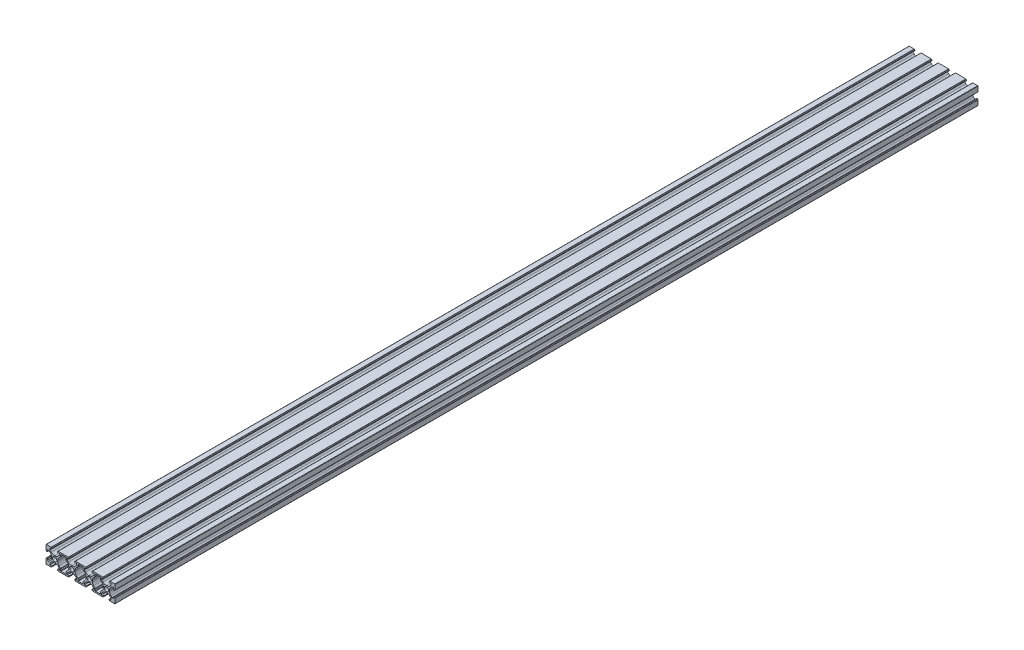
SolidWorks part; units mm, degrees
ref_plane "Plano frontal" through (0, 0, 0) normal (0, 0, 1) x (1, 0, 0)
ref_plane "Plano superior" through (0, 0, 0) normal (0, 1, 0) x (1, 0, 0)
ref_plane "Plano direito" through (0, 0, 0) normal (1, 0, 0) x (0, 0, -1)
sketch "Esboço1" plane through (0, 0, 0) normal (0, 0, 1) x (1, 0, 0)
  line L0 (-9.0343, 3.1) -> (-8.9, 3.1)
  line L3 (-10, 10) -> (-4.0657, 10)
  line L5 (-10, -10) -> (10, 10) construction
  line L6 (-10, 10) -> (10, -10) construction
  line L7 (-8.5, 3.5) -> (-8.5, 5.5)
  line L8 (-10, 0) -> (10, 0) construction
  line L9 (0, 10) -> (0, -10) construction
  line L12 (-8.5, 5.5) -> (-6.5607, 5.5)
  line L15 (-6.5607, 5.5) -> (-5.0645, 4.0038)
  line L16 (-3.6, 0.4683) -> (-3.6, 0)
  line L17 (-0.4683, 3.6) -> (0, 3.6)
  line L18 (-5.5, 6.5607) -> (-4.0038, 5.0645)
  line L21 (-5.5, 8.5) -> (-5.5, 6.5607)
  line L24 (-3.5, 8.5) -> (-5.5, 8.5)
  line L25 (-3.1, 9.0343) -> (-3.1, 8.9)
  line L44 (-10, 4.0657) -> (-10, 10)
  line L45 (-9.8828, 3.7828) -> (-9.3172, 3.2172)
  line L46 (-3.7828, 9.8828) -> (-3.2172, 9.3172)
  line L47 (-3.6, 0) -> (-2.5, 0)
  line L48 (0, 3.6) -> (0, 2.5)
  arc A0 (-3.5, 8.5) -> (-3.1, 8.9) centre (-3.5, 8.9) ccw
  arc A1 (-3.7828, 9.8828) -> (-4.0657, 10) centre (-4.0657, 9.6) ccw
  arc A2 (-10, 4.0657) -> (-9.8828, 3.7828) centre (-9.6, 4.0657) ccw
  arc A3 (-8.5, 3.5) -> (-8.9, 3.1) centre (-8.9, 3.5) cw
  arc A4 (-3.2172, 9.3172) -> (-3.1, 9.0343) centre (-3.5, 9.0343) cw
  arc A5 (-9.3172, 3.2172) -> (-9.0343, 3.1) centre (-9.0343, 3.5) ccw
  arc A6 (-3.6, 0.4683) -> (-5.0645, 4.0038) centre (-8.6, 0.4683) ccw
  arc A7 (-4.0038, 5.0645) -> (-0.4683, 3.6) centre (-0.4683, 8.6) ccw
  circle A8 centre (0, 0) radius 2.5
  point P6 (-10, 3.1)
  point P28 (-3.1, 8.5)
  point P31 (-3.1, 10)
  point P33 (-3.9, 10)
  point P36 (-10, 3.9)
  point P39 (-8.5, 3.1)
  point P42 (-3.1, 9.2)
  point P45 (-9.2, 3.1)
  point P48 (-3.6, 2.5393)
  point P51 (-2.5393, 3.6)
  dimension "D5" = 10
  dimension "D9" = 0.4
  dimension "D10" = 0.4
  dimension "D11" = 5
  dimension "D12" = 5
  dimension "D13" = 5
  dimension "D1" = 6.9
  dimension "D2" = 1.5
  dimension "D3" = 3.6
  dimension "D4" = 1.5
  dimension "D6" = 2.4
  dimension "D7" = 3.6
  dimension "D8" = 45
extrude "Ressalto-extrusão1" add sketch "Esboço1" along normal blind 1000
sketch "Esboço3" plane through (0, 0, 0) normal (1, 0, 0) x (0, 0, -1)
  line L0 (0, 0) -> (-1000, 0) construction
  dimension "D1" = 1000
pattern_circular "PadrãoCircular1" count 4 over 360 about axis through (0, 0, 0) along (0, 0, 1) of "Ressalto-extrusão1"
pattern_linear "Padrão linear1" count 4 spacing 20 along (1, 0, 0) of "Ressalto-extrusão1", "PadrãoCircular1"
sketch "Esboço4" plane through (0, 0, 0) normal (0, 0, -1) x (-1, 0, 0)
  line L0 (-13.4393, 5.5) -> (-13, 5.9393)
  line L1 (-13, 8.5) -> (-13, 5.9393)
  line L2 (-10, 10) -> (-10, -10) construction
  line L3 (-4.0657, 10) -> (-15.9343, 10) construction
  line L4 (-15.9343, -10) -> (-4.0657, -10) construction
  line L5 (-11.5, 5.5) -> (-13.4393, 5.5) construction
  line L6 (-14.5, 8.5) -> (-14.5, 6.5607) construction
  line L7 (-7, 8.5) -> (-7, 5.9393)
  line L8 (-6.5607, 5.5) -> (-7, 5.9393)
  line L9 (-13, 8.5) -> (-7, 8.5)
  line L10 (-20, 0) -> (0, 0) construction
  line L11 (-13, -8.5) -> (-7, -8.5)
  line L12 (-6.5607, -5.5) -> (-7, -5.9393)
  line L13 (-7, -8.5) -> (-7, -5.9393)
  line L14 (-13, -8.5) -> (-13, -5.9393)
  line L15 (-13.4393, -5.5) -> (-13, -5.9393)
  line L16 (-13.4393, 5.5) -> (-13.4393, -5.5)
  line L17 (-6.5607, -5.5) -> (-6.5607, 5.5)
  line L31 (-40, 0) -> (-20, 0) construction
  line L32 (-33.4393, 5.5) -> (-33, 5.9393)
  line L33 (-33, 8.5) -> (-33, 5.9393)
  line L34 (-27, 8.5) -> (-27, 5.9393)
  line L35 (-26.5607, 5.5) -> (-27, 5.9393)
  line L36 (-33, 8.5) -> (-27, 8.5)
  line L37 (-33, -8.5) -> (-27, -8.5)
  line L38 (-26.5607, -5.5) -> (-27, -5.9393)
  line L39 (-27, -8.5) -> (-27, -5.9393)
  line L40 (-33, -8.5) -> (-33, -5.9393)
  line L41 (-33.4393, -5.5) -> (-33, -5.9393)
  line L42 (-33.4393, 5.5) -> (-33.4393, -5.5)
  line L43 (-26.5607, -5.5) -> (-26.5607, 5.5)
  line L44 (-30, 10) -> (-30, -10) construction
  dimension "D1" = 45
  dimension "D2" = 1.5
  dimension "D3" = 1.5
  dimension "D4" = 2
extrude "Corte-extrusão1" cut sketch "Esboço4" against normal through all
pattern_linear "Padrão linear2" count 3 spacing 20 along (1, 0, 0) of "Corte-extrusão1"
fillet "Filete1" radius 0.4 24 edges at (13, -5.9393, 500) (13, -8.5, 500) (7, -8.5, 500) (7, -5.9393, 500) (7, 8.5, 500) (7, 5.9393, 500) (13, 8.5, 500) (13, 5.9393, 500) (33, 8.5, 500) (27, 8.5, 500) (27, 5.9393, 500) (33, 5.9393, 500) (33, -8.5, 500) (33, -5.9393, 500) (27, -5.9393, 500) (27, -8.5, 500) (47, -8.5, 500) (53, -8.5, 500) (53, 5.9393, 500) (53, 8.5, 500) (47, -5.9393, 500) (47, 8.5, 500) (47, 5.9393, 500) (53, -5.9393, 500)
fillet "Filete2" radius 0.4 4 edges at (-10, 10, 500) (70, -10, 500) (70, 10, 500) (-10, -10, 500)
